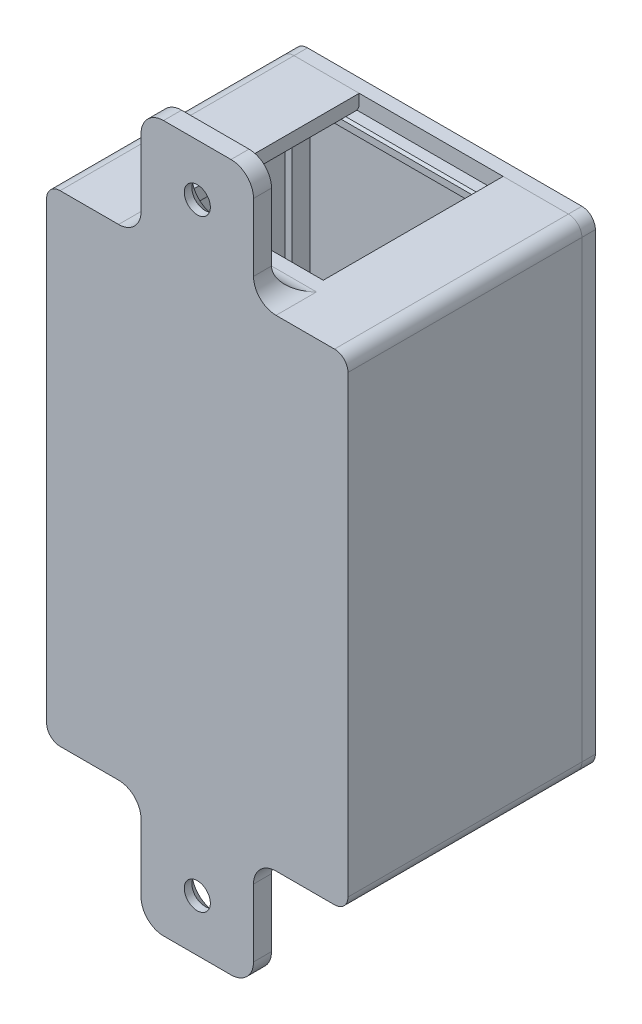
SolidWorks part; units mm, degrees
note: The reader was unsure of these and kept them because the rebuilt part matched: shared geometry of "Sketch1<3>", "Sketch9<2>".
other "Lid"
other "Body"
ref_plane "Front Plane" through (0, 0, 0) normal (0, 0, 1) x (1, 0, 0)
ref_plane "Top Plane" through (0, 0, 0) normal (0, 1, 0) x (1, 0, 0)
ref_plane "Right Plane" through (0, 0, 0) normal (1, 0, 0) x (0, 0, -1)
sketch "Sketch1" plane through (0, 0, 0) normal (0, 0, 1) x (1, 0, 0)
  line L4 (-48.8737, -136.3184) -> (-48.8737, -35.3184)
  line L5 (-48.8737, -35.3184) -> (-109.8737, -35.3184)
  line L6 (-109.8737, -35.3184) -> (-109.8737, -136.3184)
  line L7 (-109.8737, -136.3184) -> (-48.8737, -136.3184)
  line L8 (-45.8737, -139.3184) -> (-45.8737, -32.3184)
  line L9 (-45.8737, -32.3184) -> (-112.8737, -32.3184)
  line L10 (-112.8737, -32.3184) -> (-112.8737, -139.3184)
  line L11 (-112.8737, -139.3184) -> (-45.8737, -139.3184)
  line L12 (-45.8737, -139.3184) -> (-45.8737, -32.3184)
  line L13 (-45.8737, -32.3184) -> (-112.8737, -32.3184)
  line L14 (-112.8737, -32.3184) -> (-112.8737, -139.3184)
  line L15 (-112.8737, -139.3184) -> (-45.8737, -139.3184)
  line L16 (-45.8737, -85.8184) -> (-11.8426, -85.8184) construction
  line L17 (-66.8737, -32.3184) -> (-91.8737, -32.3184)
  line L18 (-66.8737, -32.3184) -> (-66.8737, -7.3184)
  line L19 (-66.8737, -7.3184) -> (-91.8737, -7.3184)
  line L20 (-91.8737, -32.3184) -> (-91.8737, -7.3184)
  line L21 (-66.8737, -164.3184) -> (-91.8737, -164.3184)
  line L22 (-91.8737, -139.3184) -> (-91.8737, -164.3184)
  line L23 (-66.8737, -139.3184) -> (-91.8737, -139.3184)
  line L24 (-66.8737, -139.3184) -> (-66.8737, -164.3184)
  point P12 (0, 0)
  point P13 (-79.3737, -32.3184)
  dimension "D3" = 25
  dimension "D4" = 25
  dimension "D1" = 6
  dimension "D2" = 3
extrude "Boss-Extrude1" add sketch "Sketch1" along normal blind 4 contours L6 L7 L4 L5 | L14 L15 L12 L13 L7 L6 L5 L4 | L24 L15 L22 L21 | L20 L13 L18 L19
extrude "Boss-Extrude2" add sketch "Sketch1<3>" against normal offset from surface (48 mm away) 8 contours L14 L15 L12 L13 L7 L6 L5 L4 offset beyond the face yes
sketch "Sketch1<3>" plane through (0, 0, 0) normal (0, 0, 1) x (1, 0, 0) same geometry as "Sketch1"
sketch "Sketch2" plane through (0, -139.3184, 0) normal (0, -1, 0) x (1, 0, 0)
  line L0 (-112.8737, -48) -> (-45.8737, -48) construction
  line L1 (-71.8737, -48) -> (-86.8737, -48)
  line L2 (-71.8737, -48) -> (-71.8737, -23)
  line L3 (-78.8737, -16) -> (-79.8737, -16)
  line L4 (-86.8737, -48) -> (-86.8737, -23)
  arc A0 (-71.8737, -23) -> (-78.8737, -16) centre (-78.8737, -23) ccw
  arc A1 (-79.8737, -16) -> (-86.8737, -23) centre (-79.8737, -23) ccw
  point P6 (-79.3737, -48)
  point P9 (-71.8737, -16)
  point P12 (-86.8737, -16)
  dimension "D3" = 7
  dimension "D1" = 15
  dimension "D2" = 32
extrude "Cut-Extrude1" cut sketch "Sketch2" against normal up to next
sketch "Sketch3" plane through (0, -32.3184, 0) normal (0, 1, 0) x (1, 0, 0)
  line L0 (-45.8737, 48) -> (-112.8737, 48) construction
  line L1 (-95.3737, 48) -> (-63.3737, 48)
  line L2 (-95.3737, 48) -> (-95.3737, 8)
  line L3 (-95.3737, 8) -> (-63.3737, 8)
  line L4 (-63.3737, 48) -> (-63.3737, 8)
  point P6 (-79.3737, 48)
  dimension "D1" = 32
  dimension "D2" = 40
extrude "Cut-Extrude2" cut sketch "Sketch3" against normal up to next
sketch "Sketch4" plane through (0, 0, 0) normal (0, 0, -1) x (-1, 0, 0)
  line L0 (66.8737, -139.3184) -> (91.8737, -166.3184) construction
  line L1 (91.8737, -139.3184) -> (91.8737, -164.3184) construction
  line L2 (91.8737, -139.3184) -> (64.9339, -164.2627) construction
  point P8 (79.3737, -152.8184)
  point P13 (0, 0)
hole_wizard "CSK for M5 Countersunk Flat Head Screw1" positions "Sketch4" profile "Sketch5" countersink size "M5" standard "ISO"
sketch "Sketch5" plane through (-79.3737, -152.8184, 0) normal (1, 0, 0) x (0, 1, 0)
  line L0 (0, 0) -> (0, 5.7425)
  line L1 (0, 5.7425) -> (2.9, 4)
  line L2 (2.9, 4) -> (2.9, 2.3)
  line L3 (2.9, 2.3) -> (5.2, 0)
  line L5 (5.2, 0) -> (0, 0)
  line L6 (-2.9, 2.3) -> (-5.2, 0) construction
  line L10 (0, 5.7425) -> (-2.9, 4) construction
  line L11 (0, -6.35) -> (0, 107.95) construction
  dimension "Hole Dia." = 5.8
  dimension "Hole Depth" = 4
  dimension "Near C'Sink Dia." = 10.4
  dimension "Near C'Sink Angle" = 90
  dimension "Drill Angle" = 118
ref_plane "Plane1" through (0, -85.8184, 0) normal (0, -1, 0) x (-1, 0, 0)
mirror "Mirror1" about plane through (0, -85.8184, 0) normal (0, -1, 0) of "CSK for M5 Countersunk Flat Head Screw1"
fillet "Fillet1" radius 5 10 edges at (-66.8737, -7.3184, 2) (-91.8737, -7.3184, 2) (-91.8737, -32.3184, 2) (-66.8737, -32.3184, 2) (-79.3737, -32.3184, 0) (-79.3737, -139.3184, 0) (-66.8737, -139.3184, 2) (-91.8737, -139.3184, 2) (-91.8737, -164.3184, 2) (-66.8737, -164.3184, 2)
fillet "Fillet2" radius 3 4 edges at (-112.8737, -139.3184, -22) (-112.8737, -32.3184, -22) (-45.8737, -32.3184, -22) (-45.8737, -139.3184, -22)
sketch "Sketch6" plane through (0, 0, -48) normal (0, 0, -1) x (-1, 0, 0)
  line L27 (79.3737, -35.3184) -> (79.3737, -55.4812) construction
  line L28 (48.8737, -35.3184) -> (109.8737, -35.3184) construction
  line L29 (48.8737, -32.3184) -> (109.8737, -32.3184)
  line L30 (71.8737, -139.3184) -> (48.8737, -139.3184)
  line L31 (45.8737, -136.3184) -> (45.8737, -35.3184)
  line L32 (48.8737, -32.3184) -> (63.3737, -32.3184)
  line L33 (96.8737, -32.3184) -> (61.8737, -32.3184) construction
  line L34 (45.8737, -136.3184) -> (45.8737, -35.3184)
  line L35 (48.8737, -139.3184) -> (109.8737, -139.3184)
  line L36 (61.8737, -139.3184) -> (96.8737, -139.3184) construction
  line L37 (112.8737, -136.3184) -> (112.8737, -35.3184)
  arc A18 (109.8737, -32.3184) -> (112.8737, -35.3184) centre (109.8737, -35.3184) cw
  arc A19 (112.8737, -136.3184) -> (109.8737, -139.3184) centre (109.8737, -136.3184) cw
  arc A20 (45.8737, -136.3184) -> (48.8737, -139.3184) centre (48.8737, -136.3184) ccw
  arc A21 (48.8737, -32.3184) -> (45.8737, -35.3184) centre (48.8737, -35.3184) ccw
  arc A22 (45.8737, -136.3184) -> (48.8737, -139.3184) centre (48.8737, -136.3184) ccw
  arc A23 (48.8737, -32.3184) -> (45.8737, -35.3184) centre (48.8737, -35.3184) ccw
  point P8 (79.3737, -32.3184)
  point P16 (79.3737, -139.3184)
  dimension "D1" = 0
extrude "Boss-Extrude3" add sketch "Sketch6" along normal blind 3 separate body
sketch "Sketch8" plane through (0, 0, -48) normal (0, 0, -1) x (-1, 0, 0)
  line L0 (109.8737, -136.3184) -> (48.8737, -136.3184) construction
  line L1 (109.8737, -35.3184) -> (109.8737, -136.3184) construction
  line L2 (48.8737, -35.3184) -> (109.8737, -35.3184) construction
  line L3 (48.8737, -136.3184) -> (48.8737, -35.3184) construction
  line L4 (109.8737, -136.3184) -> (48.8737, -136.3184) construction
  line L5 (109.8737, -35.3184) -> (109.8737, -136.3184) construction
  line L6 (48.8737, -35.3184) -> (109.8737, -35.3184) construction
  line L7 (48.8737, -136.3184) -> (48.8737, -35.3184) construction
  line L8 (109.3737, -135.8184) -> (49.3737, -135.8184)
  line L9 (49.3737, -135.8184) -> (49.3737, -35.8184)
  line L10 (49.3737, -35.8184) -> (109.3737, -35.8184)
  line L11 (109.3737, -35.8184) -> (109.3737, -135.8184)
  dimension "D1" = 0.5
extrude "Boss-Extrude5" add sketch "Sketch8" against normal blind 3
shell "Shell5" thickness 2 removed face at (-79.3737, -85.8184, -45)
sketch "Sketch9" plane through (-109.3737, 0, 0) normal (-1, 0, 0) x (0, 0, 1)
  line L0 (-28.6, -85.8184) -> (28.6, -85.8184) construction
  line L1 (-47.5, -94.8184) -> (-45.5, -94.8184)
  line L2 (-47.5, -94.8184) -> (-47.5, -76.8184)
  line L3 (-47.5, -76.8184) -> (-45.5, -76.8184)
  line L4 (-45.5, -94.8184) -> (-45.5, -76.8184)
  line L5 (-47.5, -94.8184) -> (-45.5, -76.8184) construction
  line L6 (-47.5, -76.8184) -> (-45.5, -94.8184) construction
  line L8 (-45, -135.8184) -> (-45, -35.8184) construction
  point P0 (-46.5, -85.8184)
  dimension "D1" = 2
  dimension "D2" = 18
  dimension "D3" = 0.5
extrude "Boss-Extrude6" add sketch "Sketch9" along normal blind 3 draft 45
ref_plane "Plane2" through (-79.3737, 0, 0) normal (-1, 0, 0) x (0, 0, 1)
mirror "Mirror2" about plane through (-79.3737, 0, 0) normal (-1, 0, 0) of "Boss-Extrude6"
extrude "Cut-Extrude3" cut sketch "Sketch9<2>" along normal blind 3 draft 45 from surface at 0.5 starting at face at (-109.8737, -85.8184, -24)
sketch "Sketch9<2>" plane through (-109.3737, 0, 0) normal (-1, 0, 0) x (0, 0, 1) same geometry as "Sketch9"
mirror "Mirror3" about plane through (-79.3737, 0, 0) normal (-1, 0, 0) of "Cut-Extrude3"
chamfer "Chamfer1" distance 0.5 angle 45 4 edges at (-79.3737, -35.8184, -45) (-109.3737, -85.8184, -45) (-79.3737, -135.8184, -45) (-49.3737, -85.8184, -45)
chamfer "Chamfer2" distance 0.5 angle 45 6 edges at (-56.1237, -35.3184, -48) (-60.3737, -136.3184, -48) (-48.8737, -85.8184, -48) (-98.3737, -136.3184, -48) (-109.8737, -85.8184, -48) (-102.6237, -35.3184, -48)
